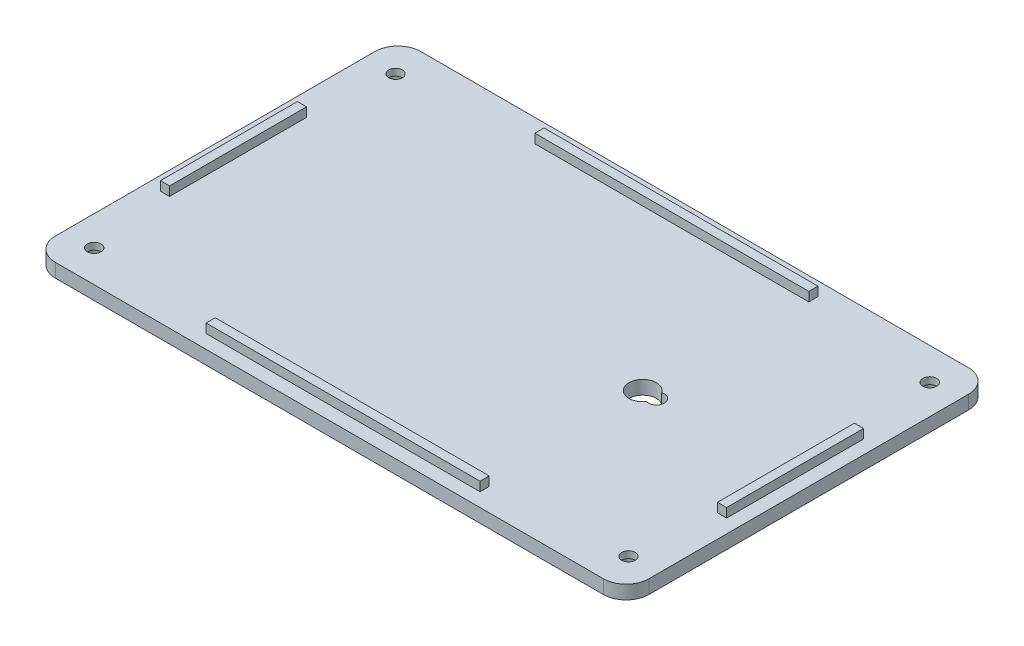
SolidWorks part; units mm, degrees
ref_plane "Спереди" through (0, 0, 0) normal (0, 0, 1) x (1, 0, 0)
ref_plane "Сверху" through (0, 0, 0) normal (0, 1, 0) x (1, 0, 0)
ref_plane "Справа" through (0, 0, 0) normal (1, 0, 0) x (0, 0, -1)
sketch "Эскиз1" plane through (0, 0, 0) normal (0, 1, 0) x (1, 0, 0)
  line L0 (-1000, 0) -> (49000, 0) construction
  line L1 (0, -1000) -> (0, 49000) construction
  line L2 (65, -1000) -> (65, 49000) construction
  line L3 (-65, -1000) -> (-65, 49000) construction
  line L4 (-1000, -40) -> (49000, -40) construction
  line L5 (-1000, 40) -> (49000, 40) construction
  line L6 (-60, 40) -> (60, 40)
  line L7 (65, 35) -> (65, -35)
  line L8 (60, -40) -> (-60, -40)
  line L9 (-65, -35) -> (-65, 35)
  arc A0 (60, 40) -> (65, 35) centre (60, 35) cw
  arc A1 (65, -35) -> (60, -40) centre (60, -35) cw
  arc A2 (-60, -40) -> (-65, -35) centre (-60, -35) cw
  arc A3 (-60, 40) -> (-65, 35) centre (-60, 35) ccw
  point P19 (65, 40)
  point P22 (65, -40)
  point P25 (-65, -40)
  point P28 (-65, 40)
extrude "Бобышка-Вытянуть1" add sketch "Эскиз1" along normal blind 3
sketch "Эскиз7" plane through (0, 0, 0) normal (0, -1, 0) x (1, 0, 0)
  line L0 (-1000, 0) -> (49000, 0) construction
  line L1 (0, -1000) -> (0, 49000) construction
  line L2 (28.6224, -1008.3644) -> (28.6224, 48991.6356) construction
  arc A0 (31.112, 1.6739) -> (31.112, -1.6739) centre (28.6224, 0) ccw
  arc A1 (31.112, -1.6739) -> (31.112, 1.6739) centre (31.6224, 0) ccw
extrude "Вырез-Вытянуть2" cut sketch "Эскиз7" against normal blind 15
sketch "Эскиз8" plane through (0, 3, 0) normal (0, 1, 0) x (1, 0, 0)
  line L0 (-1000, 0) -> (49000, 0) construction
  line L1 (0, -1000) -> (0, 49000) construction
  line L2 (58.5, -1000) -> (58.5, 49000) construction
  line L3 (-58.5, -1000) -> (-58.5, 49000) construction
  line L4 (-1000, -33) -> (49000, -33) construction
  line L5 (-1000, 33) -> (49000, 33) construction
  circle A0 centre (-58.5, 33) radius 1.5
  circle A1 centre (58.5, 33) radius 1.5
  circle A2 centre (58.5, -33) radius 1.5
  circle A3 centre (-58.5, -33) radius 1.5
  dimension "D1" = 58.5
  dimension "D2" = 58.5
  dimension "D3" = 33
  dimension "D4" = 33
extrude "Вырез-Вытянуть3" cut sketch "Эскиз8" against normal blind 10
sketch "Эскиз9" plane through (0, 0, 0) normal (0, -1, 0) x (1, 0, 0)
  circle A0 centre (-58.5, 33) radius 2.5
  circle A1 centre (58.5, 33) radius 2.5
  circle A2 centre (58.5, -33) radius 2.5
  circle A3 centre (-58.5, -33) radius 2.5
extrude "Вырез-Вытянуть4" cut sketch "Эскиз9" against normal blind 1.5
sketch "Эскиз10" plane through (0, 3, 0) normal (0, 1, 0) x (1, 0, 0)
  line L0 (-1044.3102, 40) -> (48955.6898, 40) construction
  line L2 (-1036.5149, -40) -> (48963.4851, -40) construction
  line L4 (-65, -993.9142) -> (-65, 49006.0858) construction
  line L6 (65, -996.9229) -> (65, 49003.0771) construction
  line L8 (-62, -993.9142) -> (-62, 49006.0858) construction
  line L9 (62, -996.9229) -> (62, 49003.0771) construction
  line L10 (-1044.3102, 37) -> (48955.6898, 37) construction
  line L11 (-1036.5149, -37) -> (48963.4851, -37) construction
  line L12 (-1000, 0) -> (49000, 0) construction
  line L14 (-60, -15) -> (-60, 15)
  line L15 (-30, 35) -> (30, 35)
  line L16 (0, -1000) -> (0, 49000) construction
  line L17 (30, -1000) -> (30, 49000) construction
  line L18 (-30, -1000) -> (-30, 49000) construction
  line L19 (-30, 37) -> (-30, 35)
  line L20 (-30, 37) -> (30, 37)
  line L21 (30, 37) -> (30, 35)
  line L22 (-30, -35) -> (-30, -37)
  line L23 (-30, -37) -> (30, -37)
  line L24 (30, -37) -> (30, -35)
  line L25 (-30, -35) -> (30, -35)
  line L26 (-1000, -15) -> (49000, -15) construction
  line L27 (-1000, 15) -> (49000, 15) construction
  line L28 (-60, 15) -> (-62, 15)
  line L29 (-62, 15) -> (-62, -15)
  line L30 (-62, -15) -> (-60, -15)
  line L31 (60, 15) -> (62, 15)
  line L32 (62, 15) -> (62, -15)
  line L33 (62, -15) -> (60, -15)
  line L34 (60, -15) -> (60, 15)
  point P16 (-1044.3102, 35)
  point P17 (48955.6898, 35)
  point P18 (-60, -993.9142)
  point P19 (-60, 49006.0858)
  point P20 (60, -996.9229)
  point P21 (60, 49003.0771)
  point P22 (-1036.5149, -35)
  point P23 (48963.4851, -35)
  dimension "D1" = 3
  dimension "D2" = 3
  dimension "D3" = 3
  dimension "D4" = 3
  dimension "D5" = 15
  dimension "D8" = 15
  dimension "D9" = 30
  dimension "D10" = 30
extrude "Бобышка-Вытянуть2" add sketch "Эскиз10" along normal blind 2
